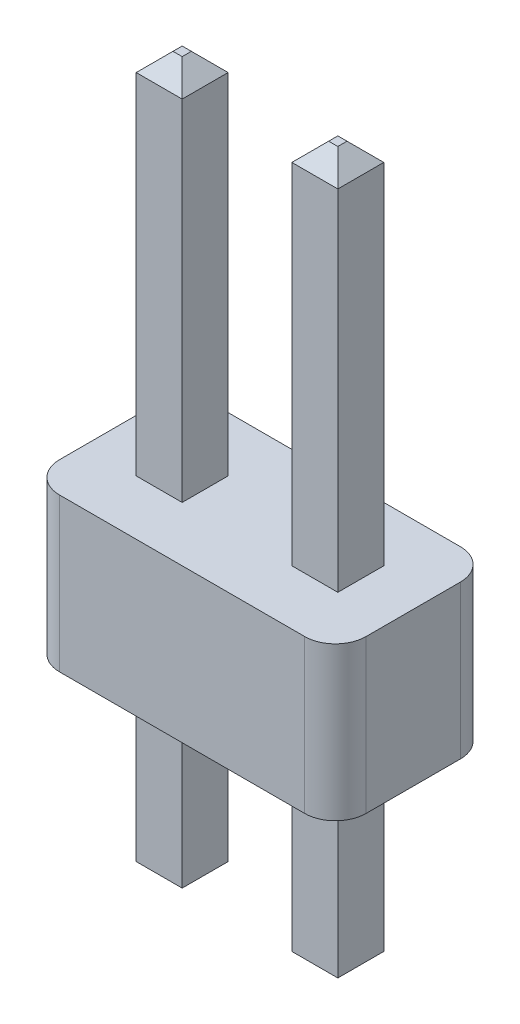
SolidWorks part; units mm, degrees
ref_plane "Front Plane" through (0, 0, 0) normal (0, 0, 1) x (1, 0, 0)
ref_plane "Top Plane" through (0, 0, 0) normal (0, 1, 0) x (1, 0, 0)
ref_plane "Right Plane" through (0, 0, 0) normal (1, 0, 0) x (0, 0, -1)
ref_plane "Plane1" through (0, 0, 0) normal (0, 1, 0) x (-1, 0, 0)
sketch "Sketch1" plane through (0, 0, 0) normal (0, 1, 0) x (-1, 0, 0)
  line L0 (-2, 1.27) -> (2, 1.27)
  line L1 (2.5, 0.77) -> (2.5, -0.77)
  line L2 (2, -1.27) -> (-2, -1.27)
  line L3 (-2.5, -0.77) -> (-2.5, 0.77)
  line L4 (0, 55) -> (0, -55) construction
  line L5 (55, 0) -> (-55, 0) construction
  arc A0 (2.5, 0.77) -> (2, 1.27) centre (2, 0.77) ccw
  arc A1 (2, -1.27) -> (2.5, -0.77) centre (2, -0.77) ccw
  arc A2 (-2.5, -0.77) -> (-2, -1.27) centre (-2, -0.77) ccw
  arc A3 (-2, 1.27) -> (-2.5, 0.77) centre (-2, 0.77) ccw
  dimension "D5" = 0.5
  dimension "D1" = 5
  dimension "D2" = 2.54
  dimension "D3" = 2.5
  dimension "D4" = 1.27
extrude "Boss-Extrude1" add sketch "Sketch1" along normal blind 2.5
ref_plane "Plane2" through (0, 0, 0) normal (0, 1, 0) x (-1, 0, 0)
sketch "Sketch2" plane through (0, 0, 0) normal (0, 1, 0) x (-1, 0, 0)
  line L0 (0.895, 0.375) -> (1.645, 0.375)
  line L1 (1.645, 0.375) -> (1.645, -0.375)
  line L2 (1.645, -0.375) -> (0.895, -0.375)
  line L3 (0.895, -0.375) -> (0.895, 0.375)
  line L4 (-0.895, -0.375) -> (-1.645, -0.375)
  line L5 (-1.645, -0.375) -> (-1.645, 0.375)
  line L6 (-1.645, 0.375) -> (-0.895, 0.375)
  line L7 (-0.895, 0.375) -> (-0.895, -0.375)
  line L8 (-1.645, 0.375) -> (-0.895, -0.375) construction
  line L9 (0.895, -0.375) -> (1.645, 0.375) construction
  line L10 (1.375, 0) -> (-1.375, 0) construction
  line L11 (0, 1.375) -> (0, -1.375) construction
  point P8 (-1.27, 0)
  point P9 (1.27, 0)
  dimension "D1" = 2.54
  dimension "D2" = 0.75
  dimension "D3" = 1.27
extrude "Boss-Extrude2" add sketch "Sketch2" along normal blind 8.5 and the other way blind 3.25
chamfer "Chamfer1" distance 0.3 angle 45 16 edges at (-1.645, 8.5, 0) (-1.27, 8.5, -0.375) (-0.895, 8.5, 0) (-1.27, 8.5, 0.375) (0.895, 8.5, 0) (1.27, 8.5, -0.375) (1.645, 8.5, 0) (1.27, 8.5, 0.375) (1.27, -3.25, -0.375) (1.645, -3.25, 0) (0.895, -3.25, 0) (1.27, -3.25, 0.375) (-1.27, -3.25, 0.375) (-1.645, -3.25, 0) (-0.895, -3.25, 0) (-1.27, -3.25, -0.375)
ref_plane "Plane3" through (1.27, 0, 0) normal (1, 0, 0) x (0, 0, -1)
ref_axis "Axis1" through (1.27, -3.8375, 0) along (0, 1, 0)
